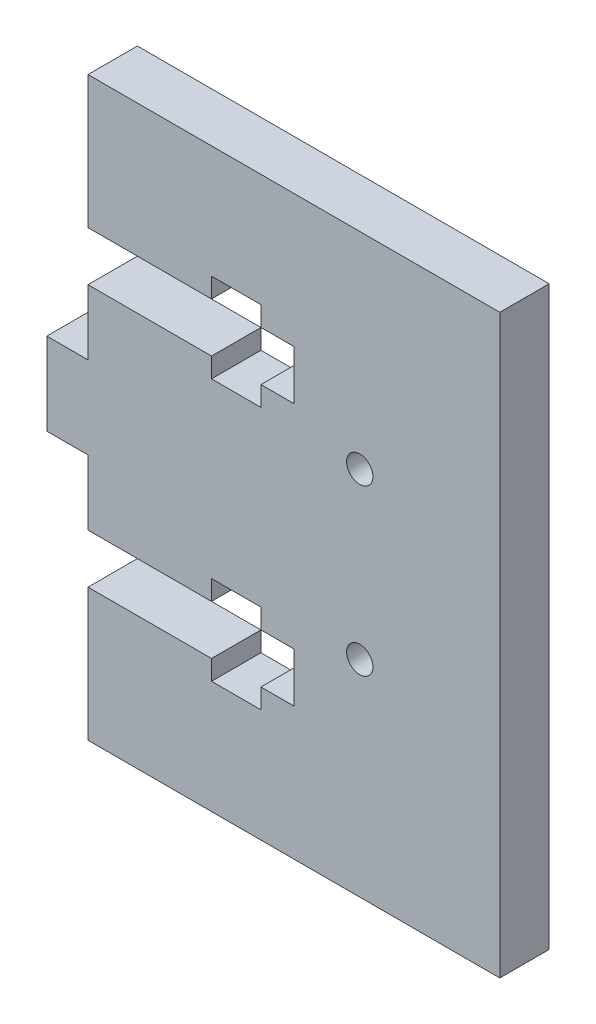
SolidWorks part; units mm, degrees
ref_plane "Front Plane" through (0, 0, 0) normal (0, 0, 1) x (1, 0, 0)
ref_plane "Top Plane" through (0, 0, 0) normal (0, 1, 0) x (1, 0, 0)
ref_plane "Right Plane" through (0, 0, 0) normal (1, 0, 0) x (0, 0, -1)
sketch "Sketch1" plane through (0, 0, 0) normal (0, 0, 1) x (1, 0, 0)
  line L0 (-97, 18.9) -> (-97, 21.3) construction
  line L1 (-68, -35) -> (-118, -35)
  line L2 (-68, -35) -> (-68, 35)
  line L3 (-68, 35) -> (-118, 35)
  line L4 (-118, -35) -> (-118, -18.9)
  line L5 (-68, -35) -> (-118, 35) construction
  line L6 (-68, 35) -> (-118, -35) construction
  line L7 (-93, 12.9) -> (-93, 18.9) construction
  line L8 (-97, 12.9) -> (-93, 12.9) construction
  line L9 (-97, 10.5) -> (-97, 12.9) construction
  line L10 (-103, 12.9) -> (-103, 10.5) construction
  line L11 (-103, 10.5) -> (-97, 10.5) construction
  line L12 (-118, 12.9) -> (-103, 12.9) construction
  line L13 (-103, 18.9) -> (-118, 18.9) construction
  line L14 (-103, 21.3) -> (-103, 18.9) construction
  line L15 (-97, 21.3) -> (-103, 21.3) construction
  line L16 (-93, 18.9) -> (-97, 18.9) construction
  line L17 (-97, 18.9) -> (-97, 21.3)
  line L18 (-93, 12.9) -> (-93, 18.9)
  line L19 (-97, 12.9) -> (-93, 12.9)
  line L20 (-97, 10.5) -> (-97, 12.9)
  line L21 (-103, 12.9) -> (-103, 10.5)
  line L22 (-103, 10.5) -> (-97, 10.5)
  line L23 (-118, 12.9) -> (-103, 12.9)
  line L24 (-103, 18.9) -> (-118, 18.9)
  line L25 (-103, 21.3) -> (-103, 18.9)
  line L26 (-97, 21.3) -> (-103, 21.3)
  line L27 (-93, 18.9) -> (-97, 18.9)
  line L28 (-118, 0) -> (-123, 0) construction
  line L29 (-118, 5) -> (-123, 5)
  line L30 (-118, -5) -> (-123, -5)
  line L31 (-123, 5) -> (-123, -5)
  line L32 (-118, 5) -> (-118, 12.9)
  line L38 (-97, -10.5) -> (-103, -10.5) construction
  line L39 (-97, -12.9) -> (-97, -10.5) construction
  line L40 (-93, -12.9) -> (-97, -12.9) construction
  line L41 (-103, -18.9) -> (-103, -21.3) construction
  line L42 (-93, -18.9) -> (-93, -12.9) construction
  line L43 (-97, -18.9) -> (-93, -18.9) construction
  line L44 (-97, -21.3) -> (-97, -18.9) construction
  line L45 (-103, -21.3) -> (-97, -21.3) construction
  line L46 (-118, -18.9) -> (-103, -18.9) construction
  line L47 (-103, -12.9) -> (-118, -12.9) construction
  line L48 (-103, -10.5) -> (-103, -12.9) construction
  line L49 (-103, -10.5) -> (-103, -12.9)
  line L50 (-97, -10.5) -> (-103, -10.5)
  line L51 (-97, -12.9) -> (-97, -10.5)
  line L52 (-93, -12.9) -> (-97, -12.9)
  line L53 (-103, -18.9) -> (-103, -21.3)
  line L54 (-93, -18.9) -> (-93, -12.9)
  line L55 (-97, -18.9) -> (-93, -18.9)
  line L56 (-97, -21.3) -> (-97, -18.9)
  line L57 (-103, -21.3) -> (-97, -21.3)
  line L58 (-118, -18.9) -> (-103, -18.9)
  line L59 (-103, -12.9) -> (-118, -12.9)
  line L60 (-118, -12.9) -> (-118, -5)
  line L61 (-118, 18.9) -> (-118, 35)
  circle A0 centre (-85, -10) radius 1.6 construction
  circle A1 centre (-85, 10) radius 1.6 construction
  circle A2 centre (-85, -10) radius 1.6
  circle A3 centre (-85, 10) radius 1.6
  point P0 (-93, 0)
  dimension "D1" = 50
  dimension "D2" = 5
  dimension "D3" = 5
  dimension "D4" = 5
extrude "Boss-Extrude1" add sketch "Sketch1" along normal blind 6
